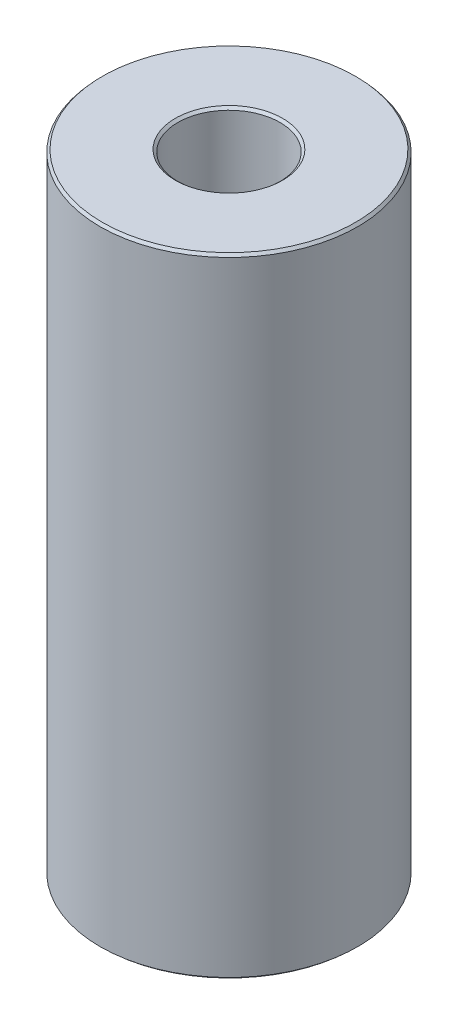
SolidWorks part; units mm, degrees
ref_plane "Front Plane" through (0, 0, 0) normal (0, 0, 1) x (1, 0, 0)
ref_plane "Top Plane" through (0, 0, 0) normal (0, 1, 0) x (1, 0, 0)
ref_plane "Right Plane" through (0, 0, 0) normal (1, 0, 0) x (0, 0, -1)
sketch "Sketch1" plane through (0, 0, 0) normal (0, 1, 0) x (1, 0, 0)
  circle A0 centre (0, 0) radius 55
  dimension "SLEEVE_OD" = 110
extrude "Boss-Extrude1" add sketch "Sketch1" along normal blind 268.2336
sketch "Sketch2" plane through (0, 0, 0) normal (0, 1, 0) x (1, 0, 0)
  circle A0 centre (0, 0) radius 21.8196
  dimension "BORE_D" = 43.6391
extrude "Cut-Extrude1" cut sketch "Sketch2" along normal through all
chamfer "Chamfer1" distance 1.1031 angle 41.433 4 edges at (0, 268.2336, 21.8196) (0, 0, 21.8196) (0, 0, 55) (0, 268.2336, 55) first distance on face at (0, 268.2336, 21.8196) first distance on face at (0, 0, 21.8196) first distance on face at (0, 268.2336, 55)
